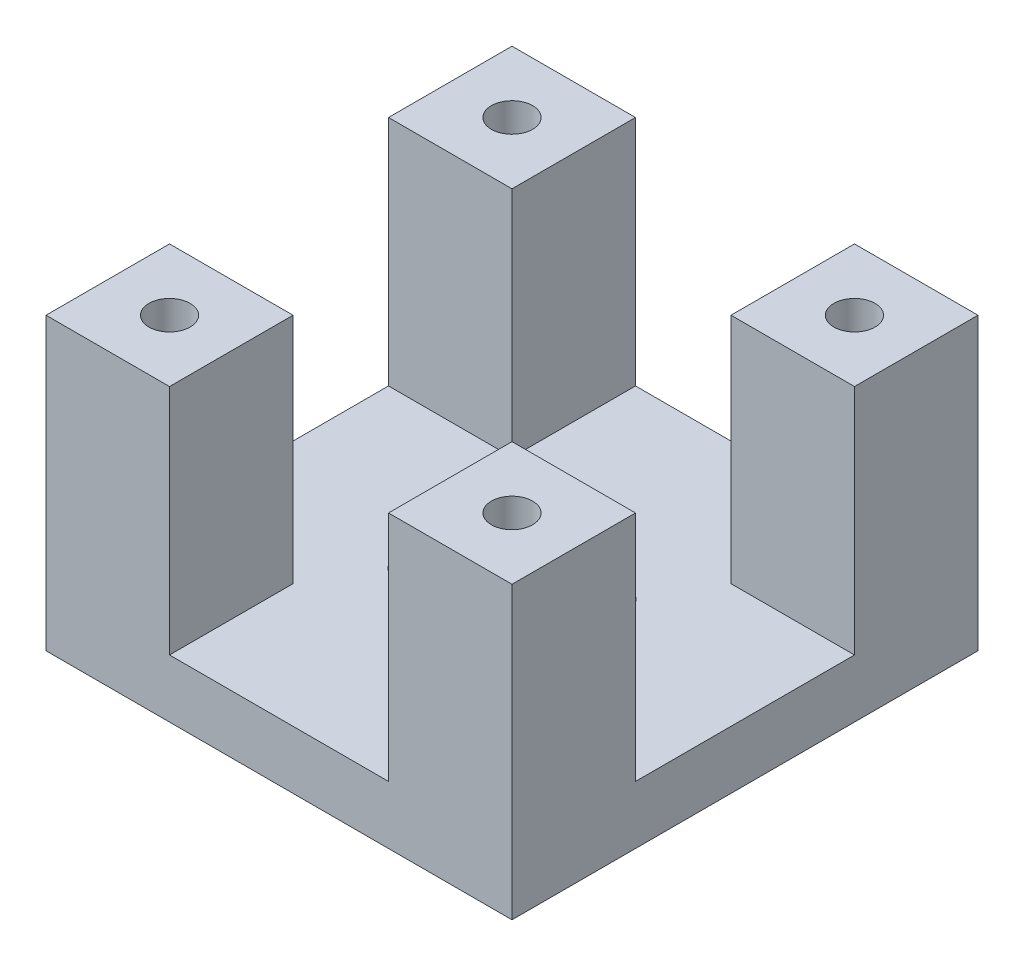
SolidWorks part; units mm, degrees
material "1060 Alloy"
ref_plane "Front" through (0, 0, 0) normal (0, 0, 1) x (1, 0, 0)
ref_plane "Top" through (0, 0, 0) normal (0, 1, 0) x (1, 0, 0)
ref_plane "Right" through (0, 0, 0) normal (1, 0, 0) x (0, 0, -1)
sketch "Sketch1" plane through (0, 0, 0) normal (0, 1, 0) x (1, 0, 0)
  line L0 (0, 0) -> (0, 86.5638) construction
  line L1 (0, 0) -> (68.5951, 68.5951) construction
  line L2 (0, 0) -> (0, 15) construction
  line L3 (0, 0) -> (35.3553, 35.3553) construction
  line L5 (-48.1053, 48.1053) -> (48.1053, 48.1053)
  line L6 (-48.1053, 48.1053) -> (-48.1053, -48.1053)
  line L7 (-48.1053, -48.1053) -> (48.1053, -48.1053)
  line L8 (48.1053, 48.1053) -> (48.1053, -48.1053)
  circle A0 centre (0, 0) radius 11
  circle A1 centre (0, 15) radius 2
  circle A2 centre (35.3553, 35.3553) radius 4.25
  circle A3 centre (12.9904, 7.5) radius 2
  circle A4 centre (12.9904, -7.5) radius 2
  circle A5 centre (0, -15) radius 2
  circle A6 centre (-12.9904, -7.5) radius 2
  circle A7 centre (-12.9904, 7.5) radius 2
  circle A8 centre (35.3553, -35.3553) radius 4.25
  circle A9 centre (-35.3553, -35.3553) radius 4.25
  circle A10 centre (-35.3553, 35.3553) radius 4.25
  dimension "D2" = 4
  dimension "D4" = 22
  dimension "D5" = 8.5
  dimension "D1" = 45
  dimension "D3" = 15
  dimension "D12" = 50
  dimension "D14" = 12.75
  dimension "D15" = 12.75
  dimension "D16" = 12.75
  dimension "D8" = 15
  dimension "D9" = 15
  dimension "D6" = 12.75
  dimension "D7" = 6
  dimension "D10" = 4
extrude "main body" add sketch "Sketch1" along normal blind 60
sketch "Sketch4" plane through (0, 60, 0) normal (0, 1, 0) x (1, 0, 0)
  line L0 (-48.1053, 48.1053) -> (48.1053, 48.1053) construction
  line L1 (-22.6053, 48.1053) -> (22.6053, 48.1053)
  line L2 (-22.6053, 48.1053) -> (-22.6053, 22.6053)
  line L3 (-22.6053, -48.1053) -> (22.6053, -48.1053)
  line L4 (22.6053, 48.1053) -> (22.6053, 22.6053)
  line L5 (-48.1053, -48.1053) -> (48.1053, -48.1053) construction
  line L6 (-48.1053, 48.1053) -> (-48.1053, -48.1053) construction
  line L7 (-48.1053, 22.6053) -> (-22.6053, 22.6053)
  line L8 (-48.1053, 22.6053) -> (-48.1053, -22.6053)
  line L9 (-48.1053, -22.6053) -> (-22.6053, -22.6053)
  line L10 (48.1053, 22.6053) -> (48.1053, -22.6053)
  line L11 (48.1053, 48.1053) -> (48.1053, -48.1053) construction
  line L12 (-22.6053, -22.6053) -> (-22.6053, -48.1053)
  line L13 (22.6053, 22.6053) -> (48.1053, 22.6053)
  line L14 (22.6053, -22.6053) -> (22.6053, -48.1053)
  line L15 (22.6053, -22.6053) -> (48.1053, -22.6053)
  dimension "D1" = 12.75
  dimension "D2" = 12.75
  dimension "D3" = 12.75
  dimension "D4" = 12.75
extrude "main mill cut" cut sketch "Sketch4" against normal blind 48
sketch "Sketch2" plane through (0, 60, 0) normal (0, 1, 0) x (1, 0, 0)
  circle A0 centre (12.9904, 7.5) radius 3.625
  circle A1 centre (0, 0) radius 5.4201 construction
  circle A2 centre (0, 15) radius 3.625
  circle A3 centre (12.9904, -7.5) radius 3.625
  circle A4 centre (0, -15) radius 3.625
  circle A5 centre (-12.9904, -7.5) radius 3.625
  circle A6 centre (-12.9904, 7.5) radius 3.625
  point P18 (0, 0)
  dimension "D1" = 7.25
extrude "motor mount bolt head countersink" cut sketch "Sketch2" against normal blind 54
equation "\"D1@Sketch2\" = \"motor mount to housing m4 head diameter\""
equation "\"D1@motor mount bolt head countersink\" = \"motor to housing distance\" - \"motor mount plate thickness\" + \"motor mount to housing m4 head depth\""
equation "\"D2@Sketch1\" = \"motor mount to housing m4 screw hole diamater\""
equation "\"D3@Sketch1\"=\"motor mount pattern diameter\"/2"
equation "\"D8@Sketch1\"=\"motor mount pattern diameter\"/2"
equation "\"D9@Sketch1\"=\"motor mount pattern diameter\"/2"
equation "\"D4@Sketch1\" = \"motor mount coupler shaft hole diameter\""
equation "\"D12@Sketch1\"= \"motor mount to housing m8 pattern diameter\" / 2"
equation "\"D6@Sketch1\" = \"motor mount to housing m8 screw post radius\""
equation "\"D14@Sketch1\" = \"motor mount to housing m8 screw post radius\""
equation "\"D15@Sketch1\" = \"motor mount to housing m8 screw post radius\""
equation "\"D16@Sketch1\" = \"motor mount to housing m8 screw post radius\""
equation "\"D5@Sketch1\" = \"motor mount to housing m8 screw hole diameter\""
equation "\"D1@Sketch4\" = \"motor mount to housing m8 screw post radius\""
equation "\"D2@Sketch4\" = \"motor mount to housing m8 screw post radius\""
equation "\"D3@Sketch4\" = \"motor mount to housing m8 screw post radius\""
equation "\"D4@Sketch4\" = \"motor mount to housing m8 screw post radius\""
equation "\"bearing OD\" = 20mm"
equation "\"bearing outer race thickness\"= 1mm"
equation "\"bearing ID\"= 10mm"
equation "\"bearing depth\"= 6mm"
equation "\"bearing inner race thickness\"= 1mm"
equation "\"seal OD\" = 20mm"
equation "\"seal ID\"= 8mm"
equation "\"seal depth\"= 6mm"
equation "\"impeller base outer diameter\"= 1.75in"
equation "\"impeller base outer thickness\"= 1mm"
equation "\"impeller base center thickness\"= 5mm"
equation "\"impeller number of vanes\"= 8"
equation "\"impeller vane outer height`\"= 4mm"
equation "\"impeller vane inner height\"= 8mm"
equation "\"impeller primary vane opening diamater\"= 10mm"
equation "\"impeller shaft bore size\"=4mm "
equation "\"impeller vane inner thickness\"= .75mm"
equation "\"impeller vane outer thickness\"= 1.5mm"
equation "\"impeller primary vane entrance angle\"= 20deg"
equation "\"impeller secondary vane entrance angle\"= 20deg"
equation "\"impeller secondary vane opening diameter\"= 10mm"
equation "\"motor to housing distance\"= 60mm"
equation "\"motor mount pattern diameter\"= 30mm"
equation "\"motor mount coupler shaft hole diameter\"= \"coupler shaft base diameter\"+ 4mm"
equation "\"motor mount to housing m8 screw hole diameter\"= 8.5mm"
equation "\"motor mount to housing m8 screw post radius\"= ( 3 * \"motor mount to housing m8 screw hole diameter\" ) / 2"
equation "\"motor mount to housing m8 pattern diameter\"= 100mm"
equation "\"motor mount to housing m4 screw hole diamater\"= 4mm"
equation "\"motor mount to housing m4 head diameter\"= 7.25mm"
equation "\"motor mount to housing m4 head depth\"= 4mm"
equation "\"motor mount plate thickness\"= 6mm + \"motor mount to housing m4 head depth\""
equation "\"housing bearing seat lip thickness\" = 2mm"
equation "\"housing base thickness\"= \"housing bearing seat lip thickness\" + \"seal depth\" + \"bearing depth\""
equation "\"housing top impeller vertical clearance\"= .5mm"
equation "\"housing top impeller horizontal clearance\"= .5mm"
equation "\"housing top impeller bottom clearance\"= 1mm"
equation "\"housing top impeller cavity height\"= \"housing top impeller bottom clearance\" + \"impeller base center thickness\" + \"impeller vane inner height\" + \"housing top impeller vertical clearance\""
equation "\"housing top impeller cavity diameter\"= 2 * \"housing top impeller horizontal clearance\" + \"impeller base outer diameter\""
equation "\"housing top impeller cavity tip height\"= \"housing top impeller bottom clearance\" + \"housing top impeller vertical clearance\" + \"impeller base outer thickness\" + \"impeller vane outer height\""
equation "\"housing top entrance OD\"= 20mm"
equation "\"housing top exit OD\"= 5mm"
equation "\"housing top o-ring channel height\"= 1.5mm"
equation "\"housing top o ring channel width\"= 1.5mm"
equation "\"housing top o-ring circumference\" = 250mm"
equation "\"housing top o-ring radius\" = (\"housing top o-ring circumference\")/(2*3.14)"
equation "\"housing top threaded inlet depth\"= 8mm"
equation "\"housing top total thickness\"= \"housing top threaded inlet depth\" + \"housing top impeller cavity height\""
equation "\"housing top total width\"= 10mm"
equation "\"housing top exit threaded diameter\"= 8mm"
equation "\"housing top exit threaded depth\"= 8mm"
equation "\"motor shaft pride\"= 32mm"
equation "\"motor shaft flat section length from tip\"= 25.7mm"
equation "\"motor shaft bore end clearance\"= 2mm"
equation "\"motor mount shaft hole depth\"= \"motor shaft pride\""
equation "\"coupler shaft set screw drill hole diameter\"= 6mm"
equation "\"coupler shaft set screw 1 distance\"= \"motor mount shaft hole depth\" / 3"
equation "\"coupler shaft set screw 2 distance\"= \"motor mount shaft hole depth\" * 4 / 5"
equation "\"coupler shaft motor shaft hole diameter\"= 8mm"
equation "\"coupler shaft base diameter\"= 18mm"
equation "\"coupler shaft base length\"= \"motor mount shaft hole depth\" + 10mm"
equation "\"coupler shaft second section diameter\"= \"bearing ID\" + \"bearing inner race thickness\" * 2"
equation "\"coupler shaft second section length\"= \"motor to housing distance\" -  \"coupler shaft base length\" - 2mm"
equation "\"coupler shaft third section diamater\"= \"bearing ID\""
equation "\"coupler shaft third section length\"= \"bearing depth\""
equation "\"coupler shaft seal section diameter\" = \"seal ID\""
equation "\"coupler shaft seal section length\" = \"housing base thickness\"+\"housing top impeller bottom clearance\"-\"bearing depth\""
equation "\"coupler shaft impeller section diameter\" = 6mm"
equation "\"coupler shaft impeller section length\" = \"impeller boss depth\"+\"impeller base center thickness\" - 1mm"
equation "\"coupler shaft impeller screw hole diameter\" = \"motor mount to housing m4 screw hole diamater\""
equation "\"coupler shaft impeller screw hole depth\" = 10mm"
